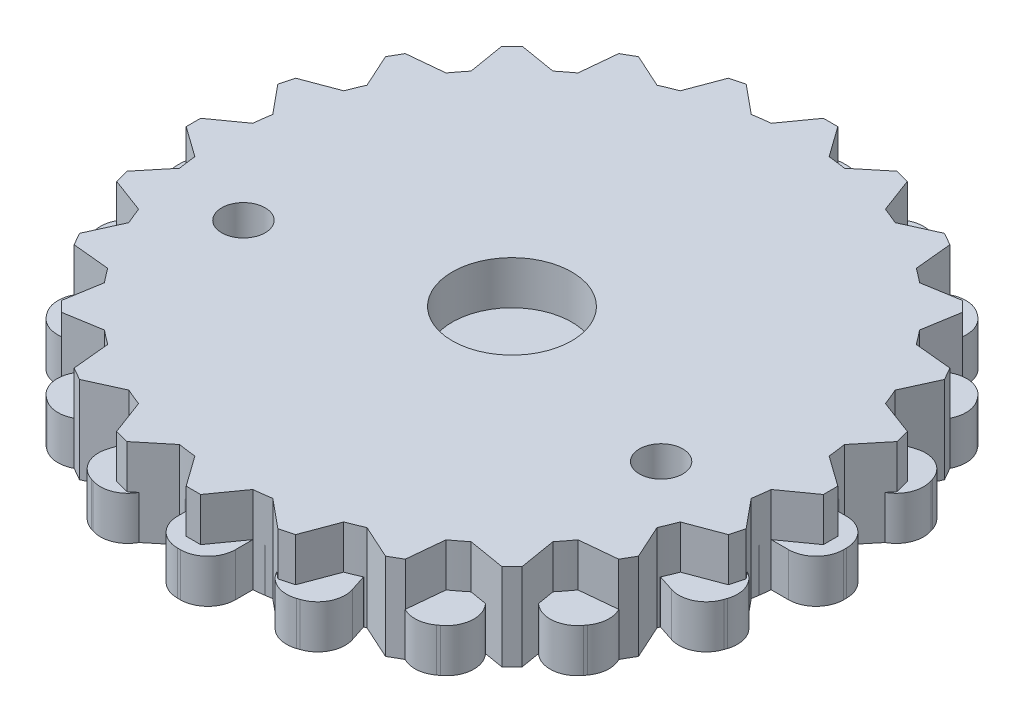
SolidWorks part; units mm, degrees
ref_plane "Front Plane" through (0, 0, 0) normal (0, 0, 1) x (1, 0, 0)
ref_plane "Top Plane" through (0, 0, 0) normal (0, 1, 0) x (1, 0, 0)
ref_plane "Right Plane" through (0, 0, 0) normal (1, 0, 0) x (0, 0, -1)
sketch "Sketch1" plane through (0, 0, 0) normal (0, 1, 0) x (1, 0, 0)
  line L111 (-0.5, 14.7462) -> (0.5, 14.7462)
  line L112 (0.5, 14.7462) -> (2, 12.5441)
  line L113 (-0.5, 14.7462) -> (-2, 12.5441)
  line L114 (6.433, 12.8885) -> (6.631, 10.2315)
  line L115 (5.567, 13.3885) -> (6.433, 12.8885)
  line L116 (5.567, 13.3885) -> (3.1669, 12.2315)
  line L117 (10.6423, 8.3132) -> (9.4853, 5.9131)
  line L118 (10.1423, 9.1792) -> (10.6423, 8.3132)
  line L119 (10.1423, 9.1792) -> (7.4853, 9.3772)
  line L120 (12, 2.2462) -> (9.798, 0.7462)
  line L121 (12, 3.2462) -> (12, 2.2462)
  line L122 (12, 3.2462) -> (9.798, 4.7462)
  line L123 (10.1423, -3.6868) -> (7.4853, -3.8849)
  line L124 (10.6423, -2.8208) -> (10.1423, -3.6868)
  line L125 (10.6423, -2.8208) -> (9.4853, -0.4208)
  line L126 (5.567, -7.8961) -> (3.1669, -6.7391)
  line L127 (6.433, -7.3961) -> (5.567, -7.8961)
  line L128 (6.433, -7.3961) -> (6.631, -4.7391)
  line L129 (-0.5, -9.2538) -> (-2, -7.0518)
  line L130 (0.5, -9.2538) -> (-0.5, -9.2538)
  line L131 (0.5, -9.2538) -> (2, -7.0518)
  line L132 (-6.433, -7.3961) -> (-6.631, -4.7391)
  line L133 (-5.567, -7.8961) -> (-6.433, -7.3961)
  line L134 (-5.567, -7.8961) -> (-3.1669, -6.7391)
  line L135 (-10.6423, -2.8208) -> (-9.4853, -0.4208)
  line L136 (-10.1423, -3.6868) -> (-10.6423, -2.8208)
  line L137 (-10.1423, -3.6868) -> (-7.4853, -3.8849)
  line L138 (-12, 3.2462) -> (-9.798, 4.7462)
  line L139 (-12, 2.2462) -> (-12, 3.2462)
  line L140 (-12, 2.2462) -> (-9.798, 0.7462)
  line L141 (-10.1423, 9.1792) -> (-7.4853, 9.3772)
  line L142 (-10.6423, 8.3132) -> (-10.1423, 9.1792)
  line L143 (-10.6423, 8.3132) -> (-9.4853, 5.9131)
  line L144 (-5.567, 13.3885) -> (-3.1669, 12.2315)
  line L145 (-6.433, 12.8885) -> (-5.567, 13.3885)
  line L146 (-6.433, 12.8885) -> (-6.631, 10.2315)
  arc A43 (-2, 12.5441) -> (-3.1669, 12.2315) centre (0, 2.7462) ccw
  arc A44 (-6.631, 10.2315) -> (-7.4853, 9.3772) centre (0, 2.7462) ccw
  arc A45 (-9.4853, 5.9131) -> (-9.798, 4.7462) centre (0, 2.7462) ccw
  arc A46 (-9.798, 0.7462) -> (-9.4853, -0.4208) centre (0, 2.7462) ccw
  arc A47 (-7.4853, -3.8849) -> (-6.631, -4.7391) centre (0, 2.7462) ccw
  arc A48 (-3.1669, -6.7391) -> (-2, -7.0518) centre (0, 2.7462) ccw
  arc A49 (2, -7.0518) -> (3.1669, -6.7391) centre (0, 2.7462) ccw
  arc A50 (6.631, -4.7391) -> (7.4853, -3.8849) centre (0, 2.7462) ccw
  arc A51 (9.4853, -0.4208) -> (9.798, 0.7462) centre (0, 2.7462) ccw
  arc A52 (9.798, 4.7462) -> (9.4853, 5.9131) centre (0, 2.7462) ccw
  arc A53 (7.4853, 9.3772) -> (6.631, 10.2315) centre (0, 2.7462) ccw
  arc A54 (3.1669, 12.2315) -> (2, 12.5441) centre (0, 2.7462) ccw
  point P6 (0, 0)
  point P8 (0, 0)
  point P9 (0, 0)
  point P12 (0, 2.7462)
  point P17 (0, 0)
  point P18 (0, 2.7462)
  point P22 (-2.5, 0.7462)
  point P63 (0, 0)
  point P68 (0, 0)
  point P69 (0, 2.7462)
  point P119 (0, 0)
  dimension "D1" = 20
  dimension "D8" = 12
sketch "Sketch2" plane through (0, 0, 0) normal (0, 1, 0) x (1, 0, 0)
  line L0 (-2, 0) -> (2, 0)
  line L1 (-23, -0.1) -> (-23, 0.1)
  line L2 (-21.1, 2) -> (-19.8997, 2)
  line L3 (-21.1, -2) -> (-19.8997, -2)
  line L4 (-20.6853, 4.6181) -> (-19.5438, 4.2472)
  line L5 (-19.4493, 8.4224) -> (-18.3078, 8.0515)
  line L6 (-21.9052, 7.0123) -> (-21.8434, 7.2025)
  line L7 (-18.2458, 10.7842) -> (-17.2748, 10.0787)
  line L8 (-15.8947, 14.0203) -> (-14.9237, 13.3148)
  line L9 (-18.6662, 13.4382) -> (-18.5486, 13.6)
  line L10 (-14.0203, 15.8947) -> (-13.3148, 14.9237)
  line L11 (-10.7842, 18.2458) -> (-10.0787, 17.2748)
  line L12 (-13.6, 18.5486) -> (-13.4382, 18.6662)
  line L13 (-8.4224, 19.4493) -> (-8.0515, 18.3078)
  line L14 (-4.6181, 20.6853) -> (-4.2472, 19.5438)
  line L15 (-7.2025, 21.8434) -> (-7.0123, 21.9052)
  line L16 (-2, 21.1) -> (-2, 19.8997)
  line L17 (2, 21.1) -> (2, 19.8997)
  line L18 (-0.1, 23) -> (0.1, 23)
  line L19 (4.6181, 20.6853) -> (4.2472, 19.5438)
  line L20 (8.4224, 19.4493) -> (8.0515, 18.3078)
  line L21 (7.0123, 21.9052) -> (7.2025, 21.8434)
  line L22 (10.7842, 18.2458) -> (10.0787, 17.2748)
  line L23 (14.0203, 15.8947) -> (13.3148, 14.9237)
  line L24 (13.4382, 18.6662) -> (13.6, 18.5486)
  line L25 (15.8947, 14.0203) -> (14.9237, 13.3148)
  line L26 (18.2458, 10.7842) -> (17.2748, 10.0787)
  line L27 (18.5486, 13.6) -> (18.6662, 13.4382)
  line L28 (19.4493, 8.4224) -> (18.3078, 8.0515)
  line L29 (20.6853, 4.6181) -> (19.5438, 4.2472)
  line L30 (21.8434, 7.2025) -> (21.9052, 7.0123)
  line L31 (21.1, 2) -> (19.8997, 2)
  line L32 (21.1, -2) -> (19.8997, -2)
  line L33 (23, 0.1) -> (23, -0.1)
  line L34 (20.6853, -4.6181) -> (19.5438, -4.2472)
  line L35 (19.4493, -8.4224) -> (18.3078, -8.0515)
  line L36 (21.9052, -7.0123) -> (21.8434, -7.2025)
  line L37 (18.2458, -10.7842) -> (17.2748, -10.0787)
  line L38 (15.8947, -14.0203) -> (14.9237, -13.3148)
  line L39 (18.6662, -13.4382) -> (18.5486, -13.6)
  line L40 (14.0203, -15.8947) -> (13.3148, -14.9237)
  line L41 (10.7842, -18.2458) -> (10.0787, -17.2748)
  line L42 (13.6, -18.5486) -> (13.4382, -18.6662)
  line L43 (8.4224, -19.4493) -> (8.0515, -18.3078)
  line L44 (4.6181, -20.6853) -> (4.2472, -19.5438)
  line L45 (7.2025, -21.8434) -> (7.0123, -21.9052)
  line L46 (2, -21.1) -> (2, -19.8997)
  line L47 (-2, -21.1) -> (-2, -19.8997)
  line L48 (0.1, -23) -> (-0.1, -23)
  line L49 (-4.6181, -20.6853) -> (-4.2472, -19.5438)
  line L50 (-8.4224, -19.4493) -> (-8.0515, -18.3078)
  line L51 (-7.0123, -21.9052) -> (-7.2025, -21.8434)
  line L52 (-10.7842, -18.2458) -> (-10.0787, -17.2748)
  line L53 (-14.0203, -15.8947) -> (-13.3148, -14.9237)
  line L54 (-13.4382, -18.6662) -> (-13.6, -18.5486)
  line L55 (-15.8947, -14.0203) -> (-14.9237, -13.3148)
  line L56 (-18.2458, -10.7842) -> (-17.2748, -10.0787)
  line L57 (-18.5486, -13.6) -> (-18.6662, -13.4382)
  line L58 (-19.4493, -8.4224) -> (-18.3078, -8.0515)
  line L59 (-20.6853, -4.6181) -> (-19.5438, -4.2472)
  line L60 (-21.8434, -7.2025) -> (-21.9052, -7.0123)
  arc A0 (-18.3078, -8.0515) -> (-17.2748, -10.0787) centre (0, 0) ccw
  arc A1 (-21.1, 2) -> (-23, 0.1) centre (-21.1, 0.1) ccw
  arc A2 (-21.1, -2) -> (-23, -0.1) centre (-21.1, -0.1) cw
  arc A3 (-20.6853, 4.6181) -> (-21.9052, 7.0123) centre (-20.0982, 6.4252) cw
  arc A4 (-19.4493, 8.4224) -> (-21.8434, 7.2025) centre (-20.0364, 6.6154) ccw
  arc A5 (-18.2458, 10.7842) -> (-18.6662, 13.4382) centre (-17.129, 12.3214) cw
  arc A6 (-15.8947, 14.0203) -> (-18.5486, 13.6) centre (-17.0115, 12.4832) ccw
  arc A7 (-14.0203, 15.8947) -> (-13.6, 18.5486) centre (-12.4832, 17.0115) cw
  arc A8 (-10.7842, 18.2458) -> (-13.4382, 18.6662) centre (-12.3214, 17.129) ccw
  arc A9 (-8.4224, 19.4493) -> (-7.2025, 21.8434) centre (-6.6154, 20.0364) cw
  arc A10 (-4.6181, 20.6853) -> (-7.0123, 21.9052) centre (-6.4252, 20.0982) ccw
  arc A11 (-2, 21.1) -> (-0.1, 23) centre (-0.1, 21.1) cw
  arc A12 (2, 21.1) -> (0.1, 23) centre (0.1, 21.1) ccw
  arc A13 (4.6181, 20.6853) -> (7.0123, 21.9052) centre (6.4252, 20.0982) cw
  arc A14 (8.4224, 19.4493) -> (7.2025, 21.8434) centre (6.6154, 20.0364) ccw
  arc A15 (10.7842, 18.2458) -> (13.4382, 18.6662) centre (12.3214, 17.129) cw
  arc A16 (14.0203, 15.8947) -> (13.6, 18.5486) centre (12.4832, 17.0115) ccw
  arc A17 (15.8947, 14.0203) -> (18.5486, 13.6) centre (17.0115, 12.4832) cw
  arc A18 (18.2458, 10.7842) -> (18.6662, 13.4382) centre (17.129, 12.3214) ccw
  arc A19 (19.4493, 8.4224) -> (21.8434, 7.2025) centre (20.0364, 6.6154) cw
  arc A20 (20.6853, 4.6181) -> (21.9052, 7.0123) centre (20.0982, 6.4252) ccw
  arc A21 (21.1, 2) -> (23, 0.1) centre (21.1, 0.1) cw
  arc A22 (21.1, -2) -> (23, -0.1) centre (21.1, -0.1) ccw
  arc A23 (20.6853, -4.6181) -> (21.9052, -7.0123) centre (20.0982, -6.4252) cw
  arc A24 (19.4493, -8.4224) -> (21.8434, -7.2025) centre (20.0364, -6.6154) ccw
  arc A25 (18.2458, -10.7842) -> (18.6662, -13.4382) centre (17.129, -12.3214) cw
  arc A26 (15.8947, -14.0203) -> (18.5486, -13.6) centre (17.0115, -12.4832) ccw
  arc A27 (14.0203, -15.8947) -> (13.6, -18.5486) centre (12.4832, -17.0115) cw
  arc A28 (10.7842, -18.2458) -> (13.4382, -18.6662) centre (12.3214, -17.129) ccw
  arc A29 (8.4224, -19.4493) -> (7.2025, -21.8434) centre (6.6154, -20.0364) cw
  arc A30 (4.6181, -20.6853) -> (7.0123, -21.9052) centre (6.4252, -20.0982) ccw
  arc A31 (2, -21.1) -> (0.1, -23) centre (0.1, -21.1) cw
  arc A32 (-2, -21.1) -> (-0.1, -23) centre (-0.1, -21.1) ccw
  arc A33 (-4.6181, -20.6853) -> (-7.0123, -21.9052) centre (-6.4252, -20.0982) cw
  arc A34 (-8.4224, -19.4493) -> (-7.2025, -21.8434) centre (-6.6154, -20.0364) ccw
  arc A35 (-10.7842, -18.2458) -> (-13.4382, -18.6662) centre (-12.3214, -17.129) cw
  arc A36 (-14.0203, -15.8947) -> (-13.6, -18.5486) centre (-12.4832, -17.0115) ccw
  arc A37 (-15.8947, -14.0203) -> (-18.5486, -13.6) centre (-17.0115, -12.4832) cw
  arc A38 (-18.2458, -10.7842) -> (-18.6662, -13.4382) centre (-17.129, -12.3214) ccw
  arc A39 (-19.4493, -8.4224) -> (-21.8434, -7.2025) centre (-20.0364, -6.6154) cw
  arc A40 (-20.6853, -4.6181) -> (-21.9052, -7.0123) centre (-20.0982, -6.4252) ccw
  arc A41 (-19.8997, -2) -> (-19.5438, -4.2472) centre (0, 0) ccw
  arc A42 (-19.5438, 4.2472) -> (-19.8997, 2) centre (0, 0) ccw
  arc A43 (-17.2748, 10.0787) -> (-18.3078, 8.0515) centre (0, 0) ccw
  arc A44 (-13.3148, 14.9237) -> (-14.9237, 13.3148) centre (0, 0) ccw
  arc A45 (-8.0515, 18.3078) -> (-10.0787, 17.2748) centre (0, 0) ccw
  arc A46 (-2, 19.8997) -> (-4.2472, 19.5438) centre (0, 0) ccw
  arc A47 (4.2472, 19.5438) -> (2, 19.8997) centre (0, 0) ccw
  arc A48 (10.0787, 17.2748) -> (8.0515, 18.3078) centre (0, 0) ccw
  arc A49 (14.9237, 13.3148) -> (13.3148, 14.9237) centre (0, 0) ccw
  arc A50 (18.3078, 8.0515) -> (17.2748, 10.0787) centre (0, 0) ccw
  arc A51 (19.8997, 2) -> (19.5438, 4.2472) centre (0, 0) ccw
  arc A52 (19.5438, -4.2472) -> (19.8997, -2) centre (0, 0) ccw
  arc A53 (17.2748, -10.0787) -> (18.3078, -8.0515) centre (0, 0) ccw
  arc A54 (13.3148, -14.9237) -> (14.9237, -13.3148) centre (0, 0) ccw
  arc A55 (8.0515, -18.3078) -> (10.0787, -17.2748) centre (0, 0) ccw
  arc A56 (2, -19.8997) -> (4.2472, -19.5438) centre (0, 0) ccw
  arc A57 (-10.0787, -17.2748) -> (-8.0515, -18.3078) centre (0, 0) ccw
  arc A58 (-4.2472, -19.5438) -> (-2, -19.8997) centre (0, 0) ccw
  arc A59 (-14.9237, -13.3148) -> (-13.3148, -14.9237) centre (0, 0) ccw
  point P6 (0, 0)
  point P10 (-23, 2)
  point P170 (0, 0)
  dimension "D1" = 40
  dimension "D4" = 1.9
  dimension "D5" = 20
extrude "Boss-Extrude3" add sketch "Sketch2" along normal blind 3 contours L55 A59 L53 A36 L54 A35 L52 A57 L50 A34 L51 A33 L49 A58 L47 A32 L48 A31 L46 A56 L44 A30 L45 A29 L43 A55 L41 A28 L42 A27 L40 A54 L38 A26 L39 A25 L37 A53 L35 A24 L36 A23 L34 A52 L32 A22 L33 A21 region at (-22.3495, 0, 0)
sketch "Sketch3" plane through (0, 0, 0) normal (0, 1, 0) x (1, 0, 0)
  line L0 (-22, 0) -> (22, 0)
  line L1 (22, -0.5) -> (22, 0.5)
  line L2 (22, 0.5) -> (19.8997, 2)
  line L3 (22, -0.5) -> (19.8997, -2)
  line L4 (21.3798, -5.2111) -> (19.7393, -3.2186)
  line L5 (21.121, -6.177) -> (21.3798, -5.2111)
  line L6 (21.121, -6.177) -> (18.704, -7.0823)
  line L7 (19.3026, -10.567) -> (18.2337, -8.2178)
  line L8 (18.8026, -11.433) -> (19.3026, -10.567)
  line L9 (18.8026, -11.433) -> (16.2337, -11.6819)
  line L10 (15.9099, -15.2028) -> (15.4855, -12.657)
  line L11 (15.2028, -15.9099) -> (15.9099, -15.2028)
  line L12 (15.2028, -15.9099) -> (12.657, -15.4855)
  line L13 (11.433, -18.8026) -> (11.6819, -16.2337)
  line L14 (10.567, -19.3026) -> (11.433, -18.8026)
  line L15 (10.567, -19.3026) -> (8.2178, -18.2337)
  line L16 (6.177, -21.121) -> (7.0823, -18.704)
  line L17 (5.2111, -21.3798) -> (6.177, -21.121)
  line L18 (5.2111, -21.3798) -> (3.2186, -19.7393)
  line L19 (0.5, -22) -> (2, -19.8997)
  line L20 (-0.5, -22) -> (0.5, -22)
  line L21 (-0.5, -22) -> (-2, -19.8997)
  line L22 (-5.2111, -21.3798) -> (-3.2186, -19.7393)
  line L23 (-6.177, -21.121) -> (-5.2111, -21.3798)
  line L24 (-6.177, -21.121) -> (-7.0823, -18.704)
  line L25 (-10.567, -19.3026) -> (-8.2178, -18.2337)
  line L26 (-11.433, -18.8026) -> (-10.567, -19.3026)
  line L27 (-11.433, -18.8026) -> (-11.6819, -16.2337)
  line L28 (-15.2028, -15.9099) -> (-12.657, -15.4855)
  line L29 (-15.9099, -15.2028) -> (-15.2028, -15.9099)
  line L30 (-15.9099, -15.2028) -> (-15.4855, -12.657)
  line L31 (-18.8026, -11.433) -> (-16.2337, -11.6819)
  line L32 (-19.3026, -10.567) -> (-18.8026, -11.433)
  line L33 (-19.3026, -10.567) -> (-18.2337, -8.2178)
  line L34 (-21.121, -6.177) -> (-18.704, -7.0823)
  line L35 (-21.3798, -5.2111) -> (-21.121, -6.177)
  line L36 (-21.3798, -5.2111) -> (-19.7393, -3.2186)
  line L37 (-22, -0.5) -> (-19.8997, -2)
  line L38 (-22, 0.5) -> (-22, -0.5)
  line L39 (-22, 0.5) -> (-19.8997, 2)
  line L40 (-21.3798, 5.2111) -> (-19.7393, 3.2186)
  line L41 (-21.121, 6.177) -> (-21.3798, 5.2111)
  line L42 (-21.121, 6.177) -> (-18.704, 7.0823)
  line L43 (-19.3026, 10.567) -> (-18.2337, 8.2178)
  line L44 (-18.8026, 11.433) -> (-19.3026, 10.567)
  line L45 (-18.8026, 11.433) -> (-16.2337, 11.6819)
  line L46 (-15.9099, 15.2028) -> (-15.4855, 12.657)
  line L47 (-15.2028, 15.9099) -> (-15.9099, 15.2028)
  line L48 (-15.2028, 15.9099) -> (-12.657, 15.4855)
  line L49 (-11.433, 18.8026) -> (-11.6819, 16.2337)
  line L50 (-10.567, 19.3026) -> (-11.433, 18.8026)
  line L51 (-10.567, 19.3026) -> (-8.2178, 18.2337)
  line L52 (-6.177, 21.121) -> (-7.0823, 18.704)
  line L53 (-5.2111, 21.3798) -> (-6.177, 21.121)
  line L54 (-5.2111, 21.3798) -> (-3.2186, 19.7393)
  line L55 (-0.5, 22) -> (-2, 19.8997)
  line L56 (0.5, 22) -> (-0.5, 22)
  line L57 (0.5, 22) -> (2, 19.8997)
  line L58 (5.2111, 21.3798) -> (3.2186, 19.7393)
  line L59 (6.177, 21.121) -> (5.2111, 21.3798)
  line L60 (6.177, 21.121) -> (7.0823, 18.704)
  line L61 (10.567, 19.3026) -> (8.2178, 18.2337)
  line L62 (11.433, 18.8026) -> (10.567, 19.3026)
  line L63 (11.433, 18.8026) -> (11.6819, 16.2337)
  line L64 (15.2028, 15.9099) -> (12.657, 15.4855)
  line L65 (15.9099, 15.2028) -> (15.2028, 15.9099)
  line L66 (15.9099, 15.2028) -> (15.4855, 12.657)
  line L67 (18.8026, 11.433) -> (16.2337, 11.6819)
  line L68 (19.3026, 10.567) -> (18.8026, 11.433)
  line L69 (19.3026, 10.567) -> (18.2337, 8.2178)
  line L70 (21.121, 6.177) -> (18.704, 7.0823)
  line L71 (21.3798, 5.2111) -> (21.121, 6.177)
  line L72 (21.3798, 5.2111) -> (19.7393, 3.2186)
  arc A0 (-8.2178, -18.2337) -> (-7.0823, -18.704) centre (0, 0) ccw
  arc A1 (-12.657, -15.4855) -> (-11.6819, -16.2337) centre (0, 0) ccw
  arc A2 (-16.2337, -11.6819) -> (-15.4855, -12.657) centre (0, 0) ccw
  arc A3 (-18.704, -7.0823) -> (-18.2337, -8.2178) centre (0, 0) ccw
  arc A4 (-19.8997, -2) -> (-19.7393, -3.2186) centre (0, 0) ccw
  arc A5 (-19.7393, 3.2186) -> (-19.8997, 2) centre (0, 0) ccw
  arc A6 (-18.2337, 8.2178) -> (-18.704, 7.0823) centre (0, 0) ccw
  arc A7 (-15.4855, 12.657) -> (-16.2337, 11.6819) centre (0, 0) ccw
  arc A8 (-11.6819, 16.2337) -> (-12.657, 15.4855) centre (0, 0) ccw
  arc A9 (-7.0823, 18.704) -> (-8.2178, 18.2337) centre (0, 0) ccw
  arc A10 (-2, 19.8997) -> (-3.2186, 19.7393) centre (0, 0) ccw
  arc A11 (3.2186, 19.7393) -> (2, 19.8997) centre (0, 0) ccw
  arc A12 (8.2178, 18.2337) -> (7.0823, 18.704) centre (0, 0) ccw
  arc A13 (12.657, 15.4855) -> (11.6819, 16.2337) centre (0, 0) ccw
  arc A14 (16.2337, 11.6819) -> (15.4855, 12.657) centre (0, 0) ccw
  arc A15 (18.704, 7.0823) -> (18.2337, 8.2178) centre (0, 0) ccw
  arc A16 (19.8997, 2) -> (19.7393, 3.2186) centre (0, 0) ccw
  arc A17 (19.7393, -3.2186) -> (19.8997, -2) centre (0, 0) ccw
  arc A18 (18.2337, -8.2178) -> (18.704, -7.0823) centre (0, 0) ccw
  arc A19 (-3.2186, -19.7393) -> (-2, -19.8997) centre (0, 0) ccw
  arc A20 (2, -19.8997) -> (3.2186, -19.7393) centre (0, 0) ccw
  arc A21 (7.0823, -18.704) -> (8.2178, -18.2337) centre (0, 0) ccw
  arc A22 (11.6819, -16.2337) -> (12.657, -15.4855) centre (0, 0) ccw
  arc A23 (15.4855, -12.657) -> (16.2337, -11.6819) centre (0, 0) ccw
  point P6 (0, 0)
  point P7 (0, -12.952)
  point P8 (-6.2727, 0)
  point P9 (11.4668, 0)
  point P10 (0, 0)
  point P108 (0, 0)
  dimension "D1" = 40
  dimension "D2" = 22
  dimension "D3" = 2
  dimension "D4" = 24
extrude "Boss-Extrude5" add sketch "Sketch3" along normal blind 6 separate body contours L2 A16 L72 L71 L70 A15 L69 L68 L67 A14 L66 L65 L64 A13 L63 L62 L61 A12 L60 L59 L58 A11 L57 L56 L55 A10 L54 L53 L52 A9 L51 L50 L49 A8 L48 L47 L46 A7 L45 L44 L43 A6 L42 L41 L40 A5 L39 L38 L0 L1 | L10 A23 L9 L8 L7 A18 L6 L5 L4 A17 L3 L1 L0 L38 L37 A4 L36 L35 L34 A3 L33 L32 L31 A2 L30 L29 L28 A1 L27 L26 L25 A0 L24 L23 L22 A19 L21 L20 L19 A20 L18 L17 L16 A21 L15 L14 L13 A22 L12 L11 region at (0, 0, -8.8989) region at (0, 0, 8.8989)
extrude "Boss-Extrude6" add sketch "Sketch1" along normal blind 3 separate body
sketch "Sketch4" plane through (0, 6, 0) normal (0, 1, 0) x (1, 0, 0)
  circle A0 centre (0, 0) radius 4.125
  dimension "D1" = 8.25
extrude "Cut-Extrude1" cut sketch "Sketch4" against normal blind 10
sketch "Sketch5" plane through (0, 6, 0) normal (0, 1, 0) x (1, 0, 0)
  line L0 (-14.4217, -4.125) -> (14.4217, -4.125) construction
  circle A0 centre (-14.4217, -4.125) radius 1.5
  circle A1 centre (0, 0) radius 4.125 construction
  circle A2 centre (14.4217, -4.125) radius 1.5
  point P6 (0, 0)
  dimension "D1" = 3
  dimension "D2" = 15
  dimension "D3" = 3
  dimension "D4" = 15
extrude "Cut-Extrude2" cut sketch "Sketch5" against normal through all
